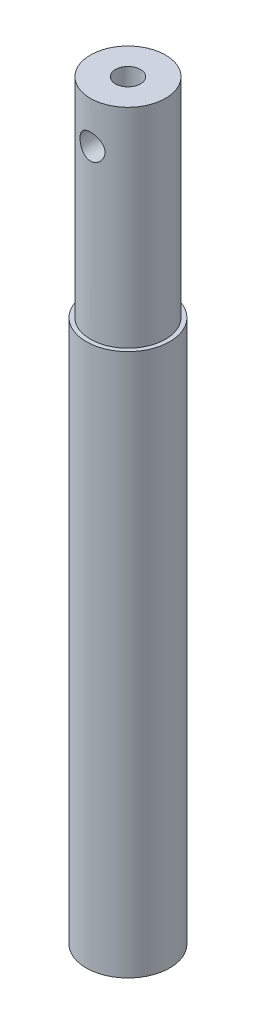
SolidWorks part; units mm, degrees
ref_plane "Front" through (0, 0, 0) normal (0, 0, 1) x (1, 0, 0)
ref_plane "Top" through (0, 0, 0) normal (0, 1, 0) x (1, 0, 0)
ref_plane "Right" through (0, 0, 0) normal (1, 0, 0) x (0, 0, -1)
sketch "Sketch1" plane through (0, 0, 0) normal (0, 1, 0) x (1, 0, 0)
  circle A0 centre (0, 0) radius 5
  circle A1 centre (0, 0) radius 2.5
  dimension "D1" = 10
  dimension "D2" = 5
extrude "Boss-Extrude1" add sketch "Sketch1" along normal blind 65
sketch "Sketch2" plane through (0, 65, 0) normal (0, 1, 0) x (1, 0, 0)
  circle A0 centre (0, 0) radius 4.5
  circle A1 centre (0, 0) radius 1.5
  dimension "D1" = 9
  dimension "D2" = 3
extrude "Boss-Extrude2" add sketch "Sketch2" along normal blind 25
sketch "Sketch4" plane through (0, 0, 0) normal (0, 0, 1) x (1, 0, 0)
  line L0 (0, 90) -> (0, 85) construction
  line L1 (1.5, 90) -> (-1.5, 90) construction
  circle A0 centre (0, 85) radius 1.5
  point P8 (0, 0)
  dimension "D1" = 3
  dimension "D2" = 5
extrude "Cut-Extrude1" cut sketch "Sketch4" against normal mid plane 65
